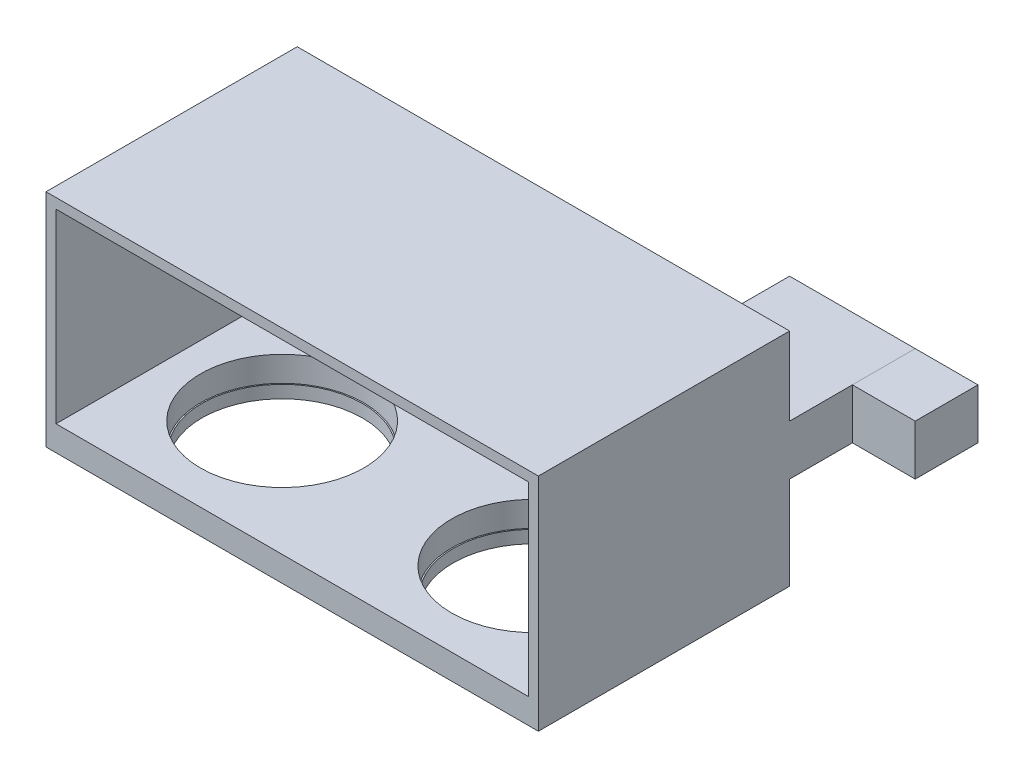
SolidWorks part; units mm, degrees
ref_plane "Front Plane" through (0, 0, 0) normal (0, 0, 1) x (1, 0, 0)
ref_plane "Top Plane" through (0, 0, 0) normal (0, 1, 0) x (1, 0, 0)
ref_plane "Right Plane" through (0, 0, 0) normal (1, 0, 0) x (0, 0, -1)
sketch "Sketch1" plane through (0, 0, 0) normal (0, 0, 1) x (1, 0, 0)
  line L1 (-24.892, -11.938) -> (24.892, -11.938)
  line L2 (-24.892, -11.938) -> (-24.892, 11.938)
  line L3 (-24.892, 11.938) -> (24.892, 11.938)
  line L4 (24.892, -11.938) -> (24.892, 11.938)
  line L5 (-24.892, -11.938) -> (24.892, 11.938) construction
  line L6 (-24.892, 11.938) -> (24.892, -11.938) construction
  point P0 (0, 0)
  dimension "D1" = 49.784
  dimension "D2" = 23.876
extrude "Boss-Extrude1" add sketch "Sketch1" against normal blind 25.4
shell "Shell1" thickness 2.54 removed face at (0, 0, 0)
sketch "Sketch2" plane through (0, -11.938, 0) normal (0, -1, 0) x (1, 0, 0)
  line L0 (0, 0) -> (0, -11.684) construction
  line L2 (-12.7, -11.684) -> (12.7, -11.684) construction
  circle A0 centre (-12.7, -11.684) radius 8.255
  circle A1 centre (12.7, -11.684) radius 8.255
  point P6 (0, -11.684)
  dimension "D2" = 16.51
  dimension "D3" = 16.51
  dimension "D1" = 25.4
  dimension "D4" = 11.684
extrude "Cut-Extrude1" cut sketch "Sketch2" against normal up to next
sketch "Sketch3" plane through (0, -11.938, 0) normal (0, -1, 0) x (1, 0, 0)
  circle A0 centre (-12.7, -11.684) radius 6.985
  circle A1 centre (-12.7, -11.684) radius 8.255
  circle A2 centre (12.7, -11.684) radius 6.985
  circle A3 centre (12.7, -11.684) radius 8.255
  dimension "D1" = 13.97
  dimension "D2" = 16.51
  dimension "D3" = 13.97
  dimension "D4" = 16.51
extrude "Boss-Extrude2" [suppressed] add sketch "Sketch3" against normal blind 1.27
sketch "Sketch4" plane through (0, 0, -22.86) normal (0, 0, 1) x (1, 0, 0)
  line L0 (-22.352, 6.736) -> (-5.842, 6.736) construction
  line L1 (-22.352, 9.398) -> (-22.352, -9.398) construction
  line L2 (22.352, 6.736) -> (5.842, 6.736) construction
  line L3 (22.352, -9.398) -> (22.352, 9.398) construction
  line L7 (22.352, 9.398) -> (-22.352, 9.398) construction
  line L8 (-5.842, -8.382) -> (5.842, -8.382)
  line L9 (-5.842, -8.382) -> (-5.842, 9.398)
  line L10 (-5.842, 9.398) -> (5.842, 9.398)
  line L11 (5.842, -8.382) -> (5.842, 9.398)
  dimension "D1" = 16.51
  dimension "D2" = 16.51
  dimension "D3" = 17.78
extrude "Cut-Extrude2" cut sketch "Sketch4" against normal up to next
sketch "Sketch5" plane through (0, -11.938, 0) normal (0, -1, 0) x (1, 0, 0)
  circle A0 centre (-12.7, -11.684) radius 8.128
  circle A1 centre (-12.7, -11.684) radius 10.541
  circle A2 centre (12.7, -11.684) radius 8.128
  circle A3 centre (12.7, -11.684) radius 10.541
  dimension "D1" = 16.256
  dimension "D2" = 21.082
  dimension "D3" = 16.256
  dimension "D4" = 21.082
extrude "Boss-Extrude3" add sketch "Sketch5" along normal blind 1.27
sketch "Sketch7" plane through (0, 0, -25.4) normal (0, 0, -1) x (-1, 0, 0)
  line L0 (-24.892, 2.5229) -> (-24.892, -2.5571)
  line L1 (-24.892, -11.938) -> (-24.892, 11.938) construction
  line L2 (-24.892, -2.5571) -> (-12.192, -2.5571)
  line L3 (-12.192, -2.5571) -> (-12.192, 2.5162)
  line L4 (-12.192, 2.5162) -> (-24.892, 2.5229)
  point P5 (-24.892, -0.0171)
  dimension "D1" = 12.7
  dimension "D2" = 5.08
extrude "Boss-Extrude4" add sketch "Sketch7" along normal blind 12.7
sketch "Sketch8" plane through (24.892, 0, 0) normal (1, 0, 0) x (0, 0, -1)
  line L0 (38.1, -2.5571) -> (25.4, -2.5571) construction
  line L1 (38.1, 2.5229) -> (31.75, 2.5229)
  line L2 (38.1, 2.5229) -> (38.1, -2.5571)
  line L3 (38.1, -2.5571) -> (31.75, -2.5571)
  line L4 (31.75, 2.5229) -> (31.75, -2.5571)
  dimension "D1" = 6.35
extrude "Boss-Extrude5" add sketch "Sketch8" along normal blind 6.35
sketch "Sketch9" plane through (-22.352, 0, 0) normal (1, 0, 0) x (0, 0, -1)
  line L0 (22.86, 9.398) -> (22.86, -9.398) construction
  line L1 (0, -9.398) -> (22.86, -9.398)
  line L2 (0, -9.398) -> (0, 9.398)
  line L3 (0, 9.398) -> (22.86, 9.398)
  line L4 (22.86, -9.398) -> (22.86, 9.398)
extrude "Cut-Extrude3" cut sketch "Sketch9" against normal blind 1.524
sketch "Sketch10" plane through (22.352, 0, 0) normal (-1, 0, 0) x (0, 0, 1)
  line L0 (-22.86, -9.398) -> (-22.86, 9.398) construction
  line L1 (0, -9.398) -> (-22.86, -9.398)
  line L2 (0, -9.398) -> (0, 9.398)
  line L3 (0, 9.398) -> (-22.86, 9.398)
  line L4 (-22.86, -9.398) -> (-22.86, 9.398)
extrude "Cut-Extrude4" cut sketch "Sketch10" against normal blind 1.524
chamfer "Chamfer1" distance 1.27 angle 45 2 edges at (-12.7, -13.208, -22.225) (12.7, -13.208, -22.225)
sketch "Sketch11" plane through (0, 11.938, 0) normal (0, 1, 0) x (1, 0, 0)
  line L1 (-24.892, 25.4) -> (24.892, 25.4)
  line L2 (-24.892, 25.4) -> (-24.892, 0)
  line L3 (-24.892, 0) -> (24.892, 0)
  line L4 (24.892, 25.4) -> (24.892, 0)
extrude "Cut-Extrude5" cut sketch "Sketch11" against normal blind 1.524
